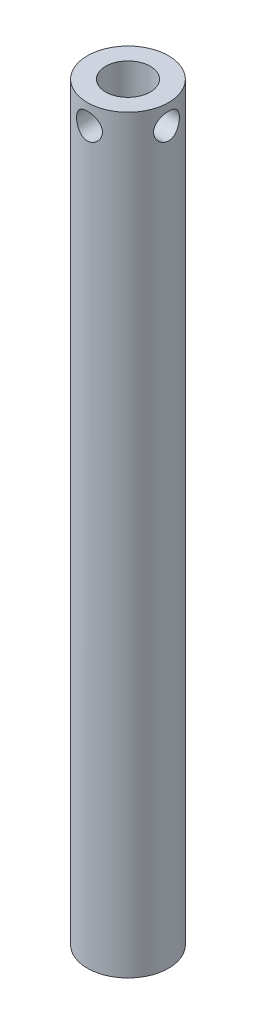
SolidWorks part; units mm, degrees
material "Brass"
ref_plane "Front Plane" through (0, 0, 0) normal (0, 0, 1) x (1, 0, 0)
ref_plane "Top Plane" through (0, 0, 0) normal (0, 1, 0) x (1, 0, 0)
ref_plane "Right Plane" through (0, 0, 0) normal (1, 0, 0) x (0, 0, -1)
sketch "Sketch1" plane through (0, 0, 0) normal (0, 1, 0) x (1, 0, 0)
  circle A0 centre (0, 0) radius 1
  circle A1 centre (0, 0) radius 0.55
  dimension "D1" = 2
  dimension "D2" = 0.45
extrude "Boss-Extrude1" add sketch "Sketch1" along normal blind 18.47
hole_wizard "#72 (0.025) Diameter Hole1" positions "3DSketch1" profile "Sketch2" hole size "#72" standard "ANSI Inch" end condition up to next
sketch3d "3DSketch1"
  line L0 (0, 18.47, 0) -> (0, 17.97, 0) construction
  line L3 (0, 17.97, 0) -> (0, 17.97, 1) construction
  line L8 (0, 17.97, 0) -> (1, 17.97, 0) construction
  point P17 (1, 17.97, 0)
  point P19 (0, 17.97, 1)
  dimension "D1" = 0.5
sketch "Sketch2" plane through (1, 17.97, 0) normal (0, 1, 0) x (0, 0, -1)
  line L0 (0, 0) -> (0, 0.45)
  line L1 (0, 0.45) -> (0.3175, 0.45)
  line L2 (0.3175, 0.45) -> (0.3175, 0)
  line L5 (0.3175, 0) -> (0, 0)
  line L11 (0, -6.35) -> (0, 107.95) construction
  dimension "Thru Hole Dia." = 0.635
  dimension "Thru Hole Depth" = 0.45
hole_wizard "#54 (0.055) Diameter Hole1" positions "Sketch4" profile "Sketch3" hole size "#54" standard "ANSI Inch"
sketch "Sketch4" plane through (0, 0, 0) normal (0, -1, 0) x (-1, 0, 0)
  point P0 (0, 0)
sketch "Sketch3" plane through (0, 0, 0) normal (1, 0, 0) x (0, 0, -1)
  line L0 (0, 0) -> (0, 4.4197)
  line L1 (0, 4.4197) -> (0.6985, 4)
  line L2 (0.6985, 4) -> (0.6985, 0)
  line L5 (0.6985, 0) -> (0, 0)
  line L10 (0, 4.4197) -> (-0.6985, 4) construction
  line L11 (0, -6.35) -> (0, 107.95) construction
  dimension "Hole Dia." = 1.397
  dimension "Hole Depth" = 4
  dimension "Drill Angle" = 118
